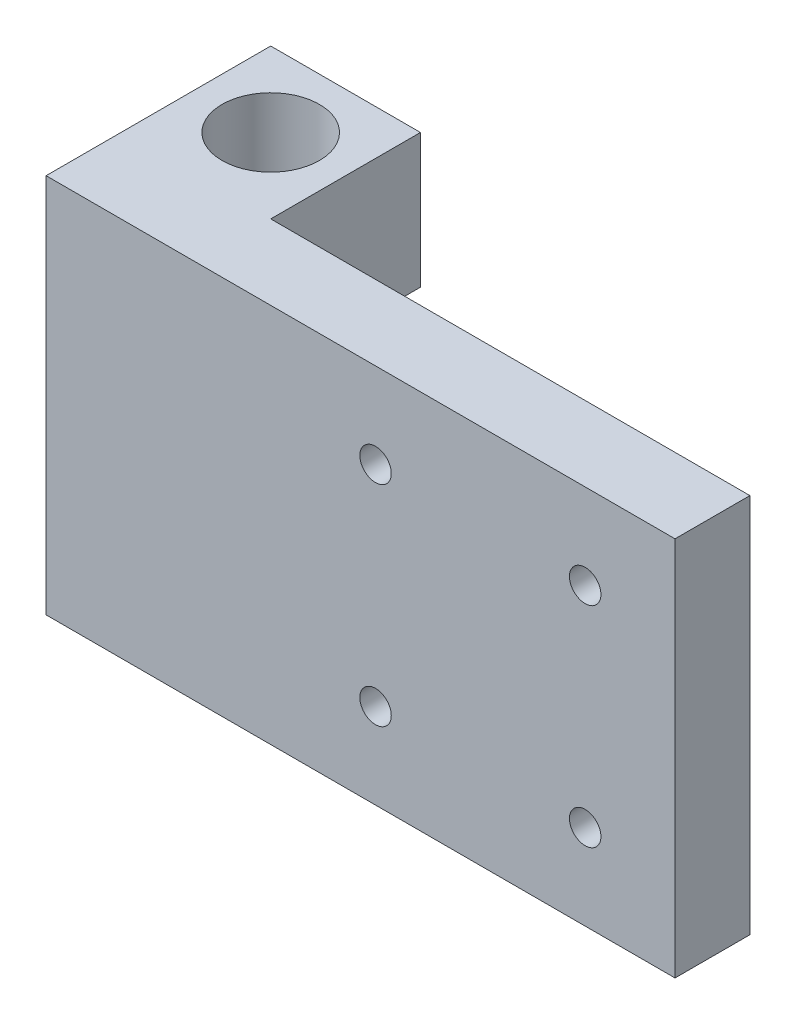
SolidWorks part; units mm, degrees
ref_plane "Front Plane" through (0, 0, 0) normal (0, 0, 1) x (1, 0, 0)
ref_plane "Top Plane" through (0, 0, 0) normal (0, 1, 0) x (1, 0, 0)
ref_plane "Right Plane" through (0, 0, 0) normal (1, 0, 0) x (0, 0, -1)
sketch "Sketch1" plane through (0, 0, 0) normal (0, 0, 1) x (1, 0, 0)
  line L1 (0, 0) -> (84, 0)
  line L2 (0, 0) -> (0, 50.8)
  line L3 (0, 50.8) -> (84, 50.8)
  line L4 (84, 0) -> (84, 50.8)
  circle A0 centre (72, 39.4) radius 2.1
  circle A1 centre (72, 11.4) radius 2.1
  circle A2 centre (44, 39.4) radius 2.1
  circle A3 centre (44, 11.4) radius 2.1
  dimension "D4" = 4.2
  dimension "D5" = 4.2
  dimension "D8" = 4.2
  dimension "D9" = 4.2
  dimension "D1" = 50.8
  dimension "D2" = 84
  dimension "D3" = 12
  dimension "D6" = 28
  dimension "D7" = 11.4
  dimension "D10" = 28
  dimension "D11" = 11.4
  dimension "D12" = 28
extrude "Boss-Extrude1" add sketch "Sketch1" along normal blind 10
sketch "Sketch3" plane through (0, 0, 0) normal (0, 0, -1) x (-1, 0, 0)
  line L0 (-84, 0) -> (-84, 50.8) construction
  line L1 (-20, 50.8) -> (0, 50.8)
  line L2 (-20, 50.8) -> (-20, 0)
  line L3 (-20, 0) -> (0, 0)
  line L4 (0, 50.8) -> (0, 0)
  line L5 (-84, 50.8) -> (0, 50.8) construction
  line L6 (0, 0) -> (-84, 0) construction
  dimension "D1" = 20
  dimension "D2" = 64
  dimension "D3" = 0
  dimension "D4" = 0
extrude "Boss-Extrude2" add sketch "Sketch3" along normal blind 20
sketch "Sketch5" plane through (0, 50.8, 0) normal (0, 1, 0) x (1, 0, 0)
  line L0 (20, 20) -> (20, 0) construction
  line L1 (0, 20) -> (20, 20) construction
  circle A0 centre (10, 10) radius 6.5
  dimension "D1" = 13
  dimension "D2" = 10
  dimension "D3" = 10
extrude "Cut-Extrude1" cut sketch "Sketch5" against normal blind 10
sketch "Sketch6" plane through (0, 0, 0) normal (0, -1, 0) x (1, 0, 0)
  line L0 (20, -20) -> (20, 0) construction
  line L1 (20, -20) -> (0, -20) construction
  circle A0 centre (10, -10) radius 6.5
  dimension "D1" = 13
  dimension "D2" = 10
  dimension "D3" = 10
extrude "Cut-Extrude2" cut sketch "Sketch6" against normal blind 10
sketch "Sketch7" plane through (0, 0, -20) normal (0, 0, -1) x (-1, 0, 0)
  line L0 (-20, 50.8) -> (-20, 0) construction
  line L1 (-10, 32.9) -> (-20, 32.9)
  line L2 (-10, 32.9) -> (-10, 17.9)
  line L3 (-10, 17.9) -> (-20, 17.9)
  line L4 (-20, 32.9) -> (-20, 17.9)
  line L6 (-20, 0) -> (0, 0) construction
  dimension "D1" = 10
  dimension "D2" = 15
  dimension "D3" = 17.9
extrude "Cut-Extrude3" cut sketch "Sketch7" against normal blind 10
equation "\"D5@Sketch1\"=\"D4@Sketch1\""
equation "\"D8@Sketch1\"=\"D4@Sketch1\""
equation "\"D9@Sketch1\"=\"D4@Sketch1\""
equation "\"D10@Sketch1\"=\"D6@Sketch1\""
equation "\"D11@Sketch1\"=\"D7@Sketch1\""
